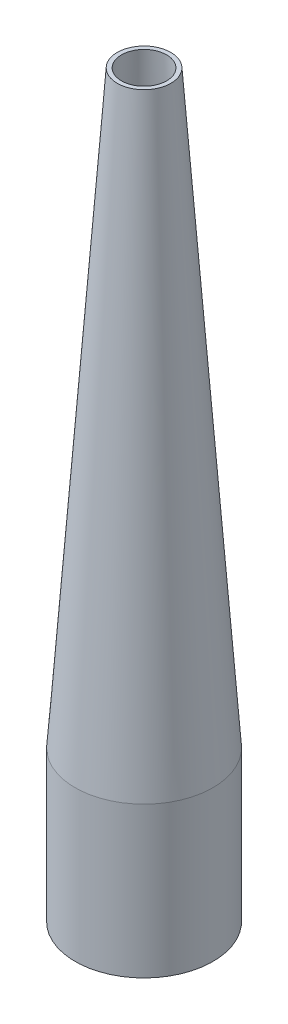
SolidWorks part; units mm, degrees
material "Hexcel AS4C (3000 Filaments)"
ref_plane "Front Plane" through (0, 0, 0) normal (0, 0, 1) x (1, 0, 0)
ref_plane "Top Plane" through (0, 0, 0) normal (0, 1, 0) x (1, 0, 0)
ref_plane "Right Plane" through (0, 0, 0) normal (1, 0, 0) x (0, 0, -1)
ref_axis "Axis1" through (0, -23.495, 0) along (0, 1, 0)
sketch "Sketch1" plane through (0, 0, 0) normal (0, 0, 1) x (1, 0, 0)
  line L0 (29.083, 0) -> (29.083, 63.5)
  line L1 (29.083, 63.5) -> (0, 469.9) construction
  line L4 (0, 311.9541) -> (11.303, 311.9541)
  line L5 (0, 311.9541) -> (0, 0)
  line L6 (0, 0) -> (29.083, 0)
  line L7 (11.303, 311.9541) -> (29.083, 63.5)
  dimension "D1" = 29.083
  dimension "D2" = 63.5
  dimension "D3" = 406.4
  dimension "D4" = 11.303
revolve "Revolve2" add sketch "Sketch1" angle 360 about axis through (0, -23.495, 0) along (0, 1, 0)
shell "Shell1" thickness 1.778 removed face at (0, 311.9541, -11.303) removed face at (0, 0, -29.083)
